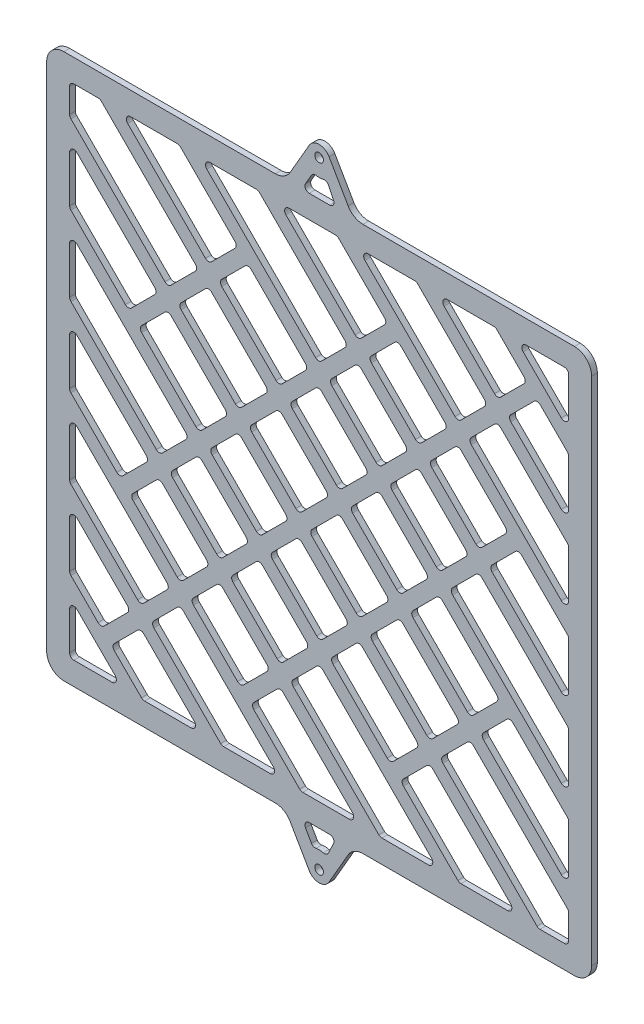
SolidWorks part; units mm, degrees
material "Thornel Mat VMA"
ref_plane "前视基准面" through (0, 0, 0) normal (0, 0, 1) x (1, 0, 0)
ref_plane "上视基准面" through (0, 0, 0) normal (0, 1, 0) x (1, 0, 0)
ref_plane "右视基准面" through (0, 0, 0) normal (1, 0, 0) x (0, 0, -1)
sketch "草图1" plane through (0, 0, 0) normal (0, 0, 1) x (1, 0, 0)
  line L1 (-95, -95) -> (95, -95)
  line L2 (-95, -95) -> (-95, 95)
  line L3 (-95, 95) -> (95, 95)
  line L4 (95, -95) -> (95, 95)
  line L5 (0, 95) -> (0, -95) construction
  line L6 (-95, 0) -> (95, 0) construction
  point P0 (0, 0)
  dimension "D1" = 190
extrude "凸台-拉伸1" add sketch "草图1" along normal blind 2
sketch "草图4" plane through (0, 0, 0) normal (0, 0, -1) x (-1, 0, 0)
  line L8 (-87, 87) -> (-87, -87)
  line L9 (-87, -87) -> (87, -87)
  line L10 (87, -87) -> (87, 87)
  line L12 (-87, 87) -> (-87, -87)
  line L14 (87, -87) -> (87, 87)
  line L16 (-87, -87) -> (87, -87)
  line L17 (87, 87) -> (-87, 87)
  line L18 (87, 87) -> (-87, 87)
  dimension "D1" = 8
sketch "草图2" plane through (0, 0, 2) normal (0, 0, 1) x (1, 0, 0)
  line L0 (0, 107.5) -> (0, -107.5) construction
  line L1 (-3.4641, 109.5) -> (-11.8357, 95)
  line L2 (95, 95) -> (-95, 95) construction
  line L3 (-11.8357, 95) -> (11.8357, 95)
  line L4 (11.8357, 95) -> (3.4641, 109.5)
  line L5 (0, 0) -> (95, 0) construction
  line L6 (95, -95) -> (95, 95) construction
  line L7 (-11.8357, -95) -> (11.8357, -95)
  line L8 (-3.4641, -109.5) -> (-11.8357, -95)
  line L9 (11.8357, -95) -> (3.4641, -109.5)
  circle A0 centre (0, -107.5) radius 1.525
  circle A1 centre (0, 107.5) radius 1.525
  arc A3 (3.4641, 109.5) -> (-3.4641, 109.5) centre (0, 107.5) ccw
  arc A4 (3.4641, -109.5) -> (-3.4641, -109.5) centre (0, -107.5) cw
  point P4 (0, 0)
  dimension "D2" = 3.05
  dimension "D4" = 8
  dimension "D1" = 215
  dimension "D5" = 60
extrude "凸台-拉伸2" add sketch "草图2" against normal up to surface (2 mm away) up to face at (0, 0, 0)
fillet "圆角1" radius 6 8 edges at (95, 95, 1) (-95, 95, 1) (-95, -95, 1) (-11.8357, -95, 1) (11.8357, -95, 1) (95, -95, 1) (-11.8357, 95, 1) (11.8357, 95, 1)
sketch "草图5" plane through (0, 0, 0) normal (0, 0, -1) x (-1, 0, 0)
  line L0 (87, 87) -> (-87, -87) construction
  line L1 (81.6967, 92.3033) -> (-92.3033, -81.6967)
  line L2 (78.1612, 95.8388) -> (-95.8388, -78.1612)
  line L3 (-87, 87) -> (0, 0) construction
  line L4 (-87, 87) -> (-87, -87)
  line L5 (-87, -87) -> (87, -87)
  line L6 (87, -87) -> (87, 87)
  line L7 (87, 87) -> (-87, 87)
  line L8 (-87, 87) -> (-87, -87)
  line L9 (-87, -87) -> (87, -87)
  line L10 (87, -87) -> (87, 87)
  line L11 (87, 87) -> (-87, 87)
  line L12 (64.3726, 109.6274) -> (-109.6274, -64.3726)
  line L13 (67.9081, 106.0919) -> (-106.0919, -67.9081)
  line L14 (50.584, 123.416) -> (-123.416, -50.584)
  line L15 (54.1195, 119.8805) -> (-119.8805, -54.1195)
  line L16 (36.7954, 137.2046) -> (-137.2046, -36.7954)
  line L17 (40.331, 133.669) -> (-133.669, -40.331)
  line L18 (23.0068, 150.9932) -> (-150.9932, -23.0068)
  line L19 (26.5424, 147.4576) -> (-147.4576, -26.5424)
  line L20 (9.2183, 164.7817) -> (-164.7817, -9.2183)
  line L21 (12.7538, 161.2462) -> (-161.2462, -12.7538)
  line L22 (161.2462, 12.7538) -> (-12.7538, -161.2462)
  line L23 (164.7817, 9.2183) -> (-9.2183, -164.7817)
  line L24 (147.4576, 26.5424) -> (-26.5424, -147.4576)
  line L25 (150.9932, 23.0068) -> (-23.0068, -150.9932)
  line L26 (133.669, 40.331) -> (-40.331, -133.669)
  line L27 (137.2046, 36.7954) -> (-36.7954, -137.2046)
  line L28 (119.8805, 54.1195) -> (-54.1195, -119.8805)
  line L29 (123.416, 50.584) -> (-50.584, -123.416)
  line L30 (106.0919, 67.9081) -> (-67.9081, -106.0919)
  line L31 (109.6274, 64.3726) -> (-64.3726, -109.6274)
  line L32 (95.8388, 78.1612) -> (-78.1612, -95.8388)
  line L33 (92.3033, 81.6967) -> (-81.6967, -92.3033)
  dimension "D5" = 14.5
  dimension "D1" = 0
  dimension "D2" = 7.5
  dimension "D3" = 5
  dimension "D4" = 6
extrude "切除-拉伸1" cut sketch "草图5" against normal up to surface (2 mm away) contours L11 L13 L8 L2 | L11 L15 L8 L12 | L11 L17 L8 L14 | L11 L19 L8 L16 | L11 L21 L8 L18 | L20 L11 L8 | L10 L32 L9 L30 | L33 L10 L11 L1 L8 L9 | L10 L31 L9 L28 | L10 L29 L9 L26 | L10 L27 L9 L24 | L10 L25 L9 L22 | L10 L23 L9 region at (0, 0, 0) region at (13.8454, 13.8454, 0) region at (-13.8454, -13.8454, 0) region at (27.6061, 27.6061, 0) region at (-27.6061, -27.6061, 0) region at (41.3498, 41.3498, 0) region at (-41.3498, -41.3498, 0) region at (55.0545, 55.0545, 0) region at (-55.0545, -55.0545, 0) region at (68.6297, 68.6297, 0) region at (-68.6297, -68.6297, 0) region at (80.8545, 80.8545, 0) region at (-80.8545, -80.8545, 0) up to face at (0, 0, 2)
sketch "草图6" plane through (0, 0, 0) normal (0, 0, -1) x (-1, 0, 0)
  line L0 (-87, 87) -> (87, -87) construction
  line L1 (-76.014, 72.4784) -> (72.4784, -76.014)
  line L2 (-61.4924, 87) -> (-87, 61.4924) construction
  line L3 (87, -61.4924) -> (61.4924, -87) construction
  line L4 (-72.4784, 76.014) -> (76.014, -72.4784)
  line L5 (76.014, -72.4784) -> (72.4784, -76.014)
  line L6 (-72.4784, 76.014) -> (-76.014, 72.4784)
  dimension "D1" = 5
extrude "凸台-拉伸3" add sketch "草图6" against normal up to surface (2 mm away) up to face at (-13.9654, -13.9654, 2)
sketch "草图7" plane through (0, 0, 0) normal (0, 0, -1) x (-1, 0, 0)
  line L0 (-67.7184, 25.6197) -> (25.6197, -67.7184) construction
  line L8 (-48.4368, 44.9013) -> (-87, 6.3381) construction
  line L10 (-69.4862, 23.8519) -> (23.8519, -69.4862)
  line L11 (-65.9506, 27.3875) -> (27.3875, -65.9506)
  line L12 (44.9013, -48.4368) -> (6.3381, -87) construction
  line L14 (-64.7273, -26.5436) -> (-26.5436, -64.7273) construction
  line L15 (-20.8597, 17.3241) -> (-87, -48.8162) construction
  line L16 (17.3241, -20.8597) -> (-48.8162, -87) construction
  line L17 (-66.4951, -28.3113) -> (-28.3113, -66.4951)
  line L18 (-62.9596, -24.7758) -> (-24.7758, -62.9596)
  line L19 (0, 0) -> (76.2258, -76.2258) construction
  line L20 (62.2254, -58.6899) -> (51.9723, -48.4368) construction
  line L21 (26.5436, 64.7273) -> (64.7273, 26.5436) construction
  line L22 (-25.6197, 67.7184) -> (67.7184, -25.6197) construction
  line L23 (24.7758, 62.9596) -> (62.9596, 24.7758)
  line L24 (28.3113, 66.4951) -> (66.4951, 28.3113)
  line L25 (-27.3875, 65.9506) -> (65.9506, -27.3875)
  line L26 (-23.8519, 69.4862) -> (69.4862, -23.8519)
  arc A0 (-69.4862, 23.8519) -> (-65.9506, 27.3875) centre (-67.7184, 25.6197) cw
  arc A1 (23.8519, -69.4862) -> (27.3875, -65.9506) centre (25.6197, -67.7184) ccw
  arc A2 (-66.4951, -28.3113) -> (-62.9596, -24.7758) centre (-64.7273, -26.5436) cw
  arc A3 (-28.3113, -66.4951) -> (-24.7758, -62.9596) centre (-26.5436, -64.7273) ccw
  arc A4 (66.4951, 28.3113) -> (62.9596, 24.7758) centre (64.7273, 26.5436) cw
  arc A5 (28.3113, 66.4951) -> (24.7758, 62.9596) centre (26.5436, 64.7273) ccw
  arc A6 (69.4862, -23.8519) -> (65.9506, -27.3875) centre (67.7184, -25.6197) cw
  arc A7 (-23.8519, 69.4862) -> (-27.3875, 65.9506) centre (-25.6197, 67.7184) ccw
  dimension "D3" = 2.5
  dimension "D5" = 29.77
  dimension "D1" = 2.5
  dimension "D2" = 2.5
  dimension "D4" = 2.5
extrude "凸台-拉伸4" add sketch "草图7" against normal up to surface (2 mm away) up to face at (-72.0494, -38.6128, 2)
sketch "草图8" plane through (0, 0, 0) normal (0, 0, -1) x (-1, 0, 0)
  line L0 (-2.6182, 102.1014) -> (-6.0622, 95)
  line L1 (-6.0622, 95) -> (6.0622, 95)
  line L2 (6.0622, 95) -> (2.092, 101.8765)
  line L3 (3.4641, 109.5) -> (10.1036, 98) construction
  line L4 (0, 107.5) -> (0, 95) construction
  line L5 (15.2998, 95) -> (89, 95) construction
  line L6 (0, 0) -> (107.9922, 0) construction
  line L7 (0, -107.5) -> (0, -95) construction
  line L8 (6.0622, -95) -> (2.092, -101.8765)
  line L9 (-6.0622, -95) -> (6.0622, -95)
  line L10 (-2.6182, -102.1014) -> (-6.0622, -95)
  arc A0 (-2.6182, 102.1014) -> (2.092, 101.8765) centre (0, 107.5) ccw
  arc A1 (-2.6182, -102.1014) -> (2.092, -101.8765) centre (0, -107.5) cw
  dimension "D2" = 12
  dimension "D1" = 5
extrude "切除-拉伸2" cut sketch "草图8" against normal up to surface (2 mm away) up to face at (-46.2536, 74.1843, 2)
fillet "圆角2" radius 1.5 184 edges at (87, 68.5635, 1) (87, 87, 1) (68.5635, 87, 1) (-68.5635, -87, 1) (-87, -68.5635, 1) (-87, -87, 1) (87, 40.9863, 1) (87, 61.4924, 1) (76.014, 72.4784, 1) (65.7609, 62.2254, 1) (-87, -40.9863, 1) (-87, -61.4924, 1) (-76.014, -72.4784, 1) (-65.7609, -62.2254, 1) (-72.4784, -76.014, 1) (-61.4924, -87, 1) (-40.9863, -87, 1) (-62.2254, -65.7609, 1) (-58.6899, -62.2254, 1) (-33.9153, -87, 1) (-13.4092, -87, 1) (-48.4368, -51.9723, 1) (-6.3381, -87, 1) (14.168, -87, 1) (-13.5989, -59.2331, 1) (-23.8519, -69.4862, 1) (51.9723, 48.4368, 1) (87, 13.4092, 1) (87, 33.9153, 1) (62.2254, 58.6899, 1) (72.4784, 76.014, 1) (61.4924, 87, 1) (40.9863, 87, 1) (62.2254, 65.7609, 1) (58.6899, 62.2254, 1) (33.9153, 87, 1) (13.4092, 87, 1) (48.4368, 51.9723, 1) (-48.4368, -44.9013, 1) (-38.1838, -34.6482, 1) (-55.6976, -17.1344, 1) (-65.9506, -27.3875, 1) (-51.9723, -48.4368, 1) (-87, -13.4092, 1) (-87, -33.9153, 1) (-62.2254, -58.6899, 1) (-10.0633, -55.6976, 1) (21.2391, -87, 1) (41.7452, -87, 1) (0.1897, -45.4445, 1) (48.8162, -87, 1) (69.3223, -87, 1) (38.5644, -56.2421, 1) (28.3113, -66.4951, 1) (45.4445, -0.1897, 1) (87, -41.7452, 1) (87, -21.2391, 1) (55.6976, 10.0633, 1) (-17.1344, -55.6976, 1) (-34.6482, -38.1838, 1) (-44.9013, -48.4368, 1) (-27.3875, -65.9506, 1) (65.9506, 27.3875, 1) (48.4368, 44.9013, 1) (38.1838, 34.6482, 1) (55.6976, 17.1344, 1) (52.1621, 13.5989, 1) (34.6482, 31.1127, 1) (24.3952, 20.8597, 1) (41.909, 3.3458, 1) (38.3735, -0.1897, 1) (20.8597, 17.3241, 1) (10.6066, 7.0711, 1) (28.1204, -10.4428, 1) (24.5849, -13.9783, 1) (7.0711, 3.5355, 1) (-3.5355, -7.0711, 1) (13.9783, -24.5849, 1) (10.4428, -28.1204, 1) (-7.0711, -10.6066, 1) (-17.3241, -20.8597, 1) (0.1897, -38.3735, 1) (-3.3458, -41.909, 1) (-20.8597, -24.3952, 1) (-31.1127, -34.6482, 1) (-13.5989, -52.1621, 1) (59.2331, 13.5989, 1) (87, -14.168, 1) (87, 6.3381, 1) (69.4862, 23.8519, 1) (42.0999, -52.7065, 1) (76.3934, -87, 1) (87, -87, 1) (87, -76.3934, 1) (52.7065, -42.0999, 1) (35.0289, -52.7065, 1) (13.9783, -31.656, 1) (3.7252, -41.909, 1) (24.7758, -62.9596, 1) (62.9596, -24.7758, 1) (41.909, -3.7252, 1) (31.656, -13.9783, 1) (52.7065, -35.0289, 1) (49.171, -38.5644, 1) (28.1204, -17.5138, 1) (17.5138, -28.1204, 1) (38.5644, -49.171, 1) (56.2421, -38.5644, 1) (87, -69.3223, 1) (87, -48.8162, 1) (66.4951, -28.3113, 1) (34.6482, 38.1838, 1) (44.9013, 48.4368, 1) (27.3875, 65.9506, 1) (17.1344, 55.6976, 1) (20.8597, 24.3952, 1) (31.1127, 34.6482, 1) (13.5989, 52.1621, 1) (3.3458, 41.909, 1) (7.0711, 10.6066, 1) (17.3241, 20.8597, 1) (-0.1897, 38.3735, 1) (-10.4428, 28.1204, 1) (-7.0711, -3.5355, 1) (3.5355, 7.0711, 1) (-13.9783, 24.5849, 1) (-24.5849, 13.9783, 1) (-20.8597, -17.3241, 1) (-10.6066, -7.0711, 1) (-28.1204, 10.4428, 1) (-38.3735, 0.1897, 1) (-34.6482, -31.1127, 1) (-24.3952, -20.8597, 1) (-41.909, -3.3458, 1) (-52.1621, -13.5989, 1) (-45.4445, 0.1897, 1) (-87, 41.7452, 1) (-87, 21.2391, 1) (-55.6976, -10.0633, 1) (23.8519, 69.4862, 1) (6.3381, 87, 1) (-14.168, 87, 1) (13.5989, 59.2331, 1) (10.0633, 55.6976, 1) (-21.2391, 87, 1) (-41.7452, 87, 1) (-0.1897, 45.4445, 1) (-59.2331, -13.5989, 1) (-87, 14.168, 1) (-87, -6.3381, 1) (-69.4862, -23.8519, 1) (-41.909, 3.7252, 1) (-31.656, 13.9783, 1) (-52.7065, 35.0289, 1) (-62.9596, 24.7758, 1) (-13.9783, 31.656, 1) (-3.7252, 41.909, 1) (-24.7758, 62.9596, 1) (-35.0289, 52.7065, 1) (-28.1204, 17.5138, 1) (-17.5138, 28.1204, 1) (-38.5644, 49.171, 1) (-49.171, 38.5644, 1) (-56.2421, 38.5644, 1) (-87, 69.3223, 1) (-87, 48.8162, 1) (-66.4951, 28.3113, 1) (-42.0999, 52.7065, 1) (-76.3934, 87, 1) (-87, 87, 1) (-87, 76.3934, 1) (-52.7065, 42.0999, 1) (-28.3113, 66.4951, 1) (-48.8162, 87, 1) (-69.3223, 87, 1) (-38.5644, 56.2421, 1) (6.0622, -95, 1) (-6.0622, -95, 1) (-6.0622, 95, 1) (6.0622, 95, 1) (2.6182, 102.1014, 1) (-2.092, 101.8765, 1) (2.6182, -102.1014, 1) (-2.092, -101.8765, 1)
